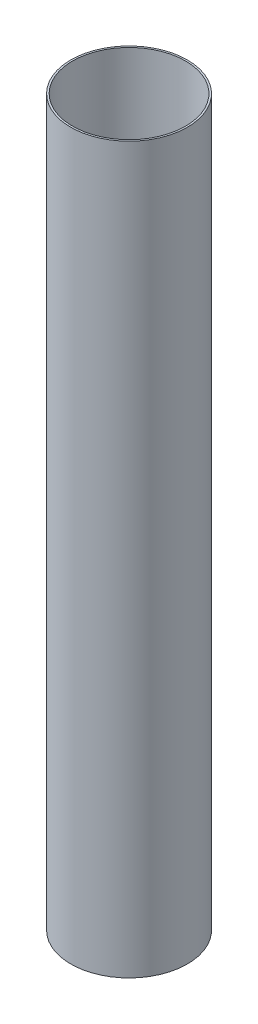
SolidWorks part; units mm, degrees
ref_plane "Front Plane" through (0, 0, 0) normal (0, 0, 1) x (1, 0, 0)
ref_plane "Top Plane" through (0, 0, 0) normal (0, 1, 0) x (1, 0, 0)
ref_plane "Right Plane" through (0, 0, 0) normal (1, 0, 0) x (0, 0, -1)
sketch "Sketch1" plane through (0, 0, 0) normal (0, 1, 0) x (1, 0, 0)
  circle A0 centre (0, 0) radius 51.1048
  circle A1 centre (0, 0) radius 49.53
  dimension "D1" = 102.2096
  dimension "D2" = 99.06
extrude "Boss-Extrude1" add sketch "Sketch1" along normal blind 635
equation "\"Body_Tube_OD\"= 4.024in"
equation "\"Body_Tube_ID\"= 3.90in"
equation "\"D1@Sketch1\"=\"Body_Tube_OD\""
equation "\"D2@Sketch1\"=\"Body_Tube_ID\""
equation "\"Fwd_Section_Length\"= 25in"
equation "\"D1@Boss-Extrude1\"=\"Fwd_Section_Length\""
